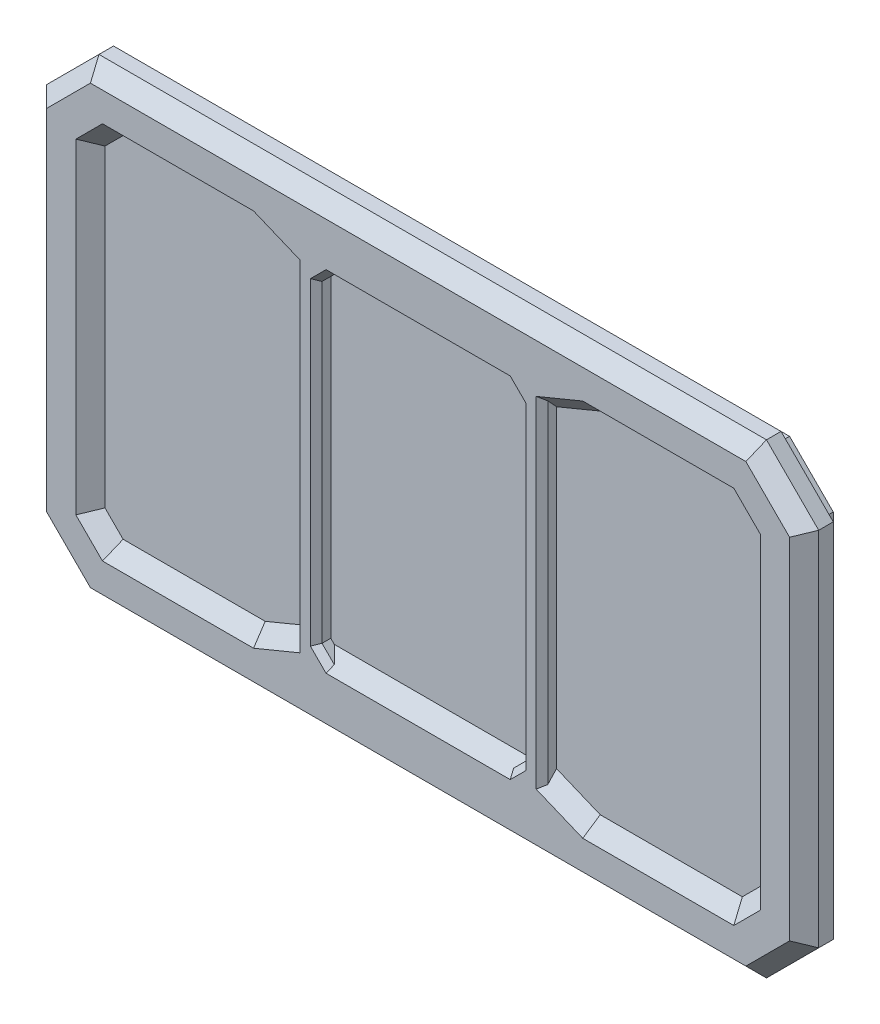
SolidWorks part; units mm, degrees
ref_plane "Plan de face" through (0, 0, 0) normal (0, 0, 1) x (1, 0, 0)
ref_plane "Plan de dessus" through (0, 0, 0) normal (0, 1, 0) x (1, 0, 0)
ref_plane "Plan de droite" through (0, 0, 0) normal (1, 0, 0) x (0, 0, -1)
sketch "Esquisse1" plane through (0, 0, 0) normal (0, 0, 1) x (1, 0, 0)
  line L0 (0, 270) -> (30, 300)
  line L1 (30, 0) -> (480, 0)
  line L2 (0, 30) -> (0, 270)
  line L3 (30, 300) -> (480, 300)
  line L4 (510, 30) -> (510, 270)
  line L5 (30, 0) -> (0, 30)
  line L6 (480, 0) -> (510, 30)
  line L7 (510, 270) -> (480, 300)
  line L8 (10, 265.8579) -> (34.1421, 290)
  line L9 (34.1421, 290) -> (475.8579, 290)
  line L10 (500, 265.8579) -> (475.8579, 290)
  line L11 (500, 34.1421) -> (500, 265.8579)
  line L12 (475.8579, 10) -> (500, 34.1421)
  line L13 (34.1421, 10) -> (475.8579, 10)
  line L14 (34.1421, 10) -> (10, 34.1421)
  line L15 (10, 34.1421) -> (10, 265.8579)
  point P0 (0, 0)
  point P1 (510, 300)
  point P2 (0, 300)
  point P3 (510, 0)
  dimension "D1" = 510
  dimension "D2" = 300
  dimension "D3" = 10
extrude "Boss.-Extru.1" add sketch "Esquisse1" along normal blind 10
sketch "Esquisse2" plane through (0, 0, 10) normal (0, 0, 1) x (1, 0, 0)
  line L17 (484.1421, 310) -> (25.8579, 310)
  line L18 (25.8579, 310) -> (-10, 274.1421)
  line L19 (-10, 274.1421) -> (-10, 25.8579)
  line L20 (-10, 25.8579) -> (25.8579, -10)
  line L21 (25.8579, -10) -> (484.1421, -10)
  line L22 (484.1421, -10) -> (520, 25.8579)
  line L23 (520, 25.8579) -> (520, 274.1421)
  line L24 (520, 274.1421) -> (484.1421, 310)
  line L25 (484.1421, 310) -> (25.8579, 310)
  line L26 (25.8579, 310) -> (-10, 274.1421)
  line L27 (-10, 274.1421) -> (-10, 25.8579)
  line L28 (-10, 25.8579) -> (25.8579, -10)
  line L29 (25.8579, -10) -> (484.1421, -10)
  line L30 (484.1421, -10) -> (520, 25.8579)
  line L31 (520, 25.8579) -> (520, 274.1421)
  line L32 (520, 274.1421) -> (484.1421, 310)
  dimension "D1" = 10
extrude "Boss.-Extru.2" add sketch "Esquisse2" along normal blind 20
sketch "Esquisse3" plane through (0, 0, 30) normal (0, 0, 1) x (1, 0, 0)
  line L8 (255, 270) -> (255, 30) construction
  line L9 (170, 270) -> (170, 30) construction
  line L10 (30, 257.5736) -> (480, 257.5736) construction
  line L11 (480, 42.4264) -> (30, 42.4264) construction
  line L12 (42.4264, 270) -> (140, 270)
  line L13 (140, 270) -> (170, 257.5736)
  line L14 (170, 257.5736) -> (170, 42.4264)
  line L15 (170, 42.4264) -> (140, 30)
  line L16 (480, 257.5736) -> (467.5736, 270)
  line L17 (467.5736, 270) -> (42.4264, 270)
  line L18 (42.4264, 270) -> (30, 257.5736)
  line L19 (30, 257.5736) -> (30, 42.4264)
  line L20 (30, 42.4264) -> (42.4264, 30)
  line L21 (42.4264, 30) -> (467.5736, 30)
  line L22 (467.5736, 30) -> (480, 42.4264)
  line L23 (480, 42.4264) -> (480, 257.5736)
  line L24 (480, 257.5736) -> (467.5736, 270)
  line L25 (467.5736, 270) -> (42.4264, 270) construction
  line L26 (42.4264, 270) -> (30, 257.5736)
  line L27 (30, 257.5736) -> (30, 42.4264)
  line L28 (30, 42.4264) -> (42.4264, 30)
  line L29 (42.4264, 30) -> (467.5736, 30) construction
  line L30 (467.5736, 30) -> (480, 42.4264)
  line L31 (480, 42.4264) -> (480, 257.5736)
  line L32 (140, 270) -> (140, 30) construction
  line L33 (42.4264, 30) -> (42.4264, 42.4264) construction
  line L34 (170, 150) -> (140, 150) construction
  line L35 (185, 270) -> (185, 30) construction
  line L36 (197.4264, 270) -> (197.4264, 30) construction
  line L37 (197.4264, 150) -> (185, 150) construction
  line L38 (197.4264, 270) -> (185, 257.5736)
  line L39 (185, 257.5736) -> (185, 42.4264)
  line L40 (185, 42.4264) -> (197.4264, 30)
  line L41 (255, 270) -> (197.4264, 270)
  line L42 (312.5736, 30) -> (197.4264, 30)
  line L43 (140, 30) -> (42.4264, 30)
  line L44 (467.5736, 270) -> (370, 270)
  line L45 (370, 270) -> (340, 257.5736)
  line L46 (255, 270) -> (312.5736, 270)
  line L47 (312.5736, 270) -> (325, 257.5736)
  line L48 (325, 257.5736) -> (325, 42.4264)
  line L49 (340, 257.5736) -> (340, 42.4264)
  line L50 (340, 42.4264) -> (370, 30)
  line L51 (325, 42.4264) -> (312.5736, 30)
  line L52 (370, 30) -> (467.5736, 30)
  dimension "D2" = 30
  dimension "D3" = 15
  dimension "D4" = 70
  dimension "D1" = 40
extrude "Enlèv. mat.-Extru.1" cut sketch "Esquisse3" against normal blind 10
chamfer "Chanfrein1" distance 10 angle 45 22 edges at (520, 150, 30) (502.0711, 7.9289, 30) (255, -10, 30) (7.9289, 7.9289, 30) (-10, 150, 30) (7.9289, 292.0711, 30) (255, 310, 30) (502.0711, 292.0711, 30) (473.7868, 263.7868, 30) (418.7868, 270, 30) (355, 263.7868, 30) (355, 36.2132, 30) (418.7868, 30, 30) (473.7868, 36.2132, 30) (480, 150, 30) (155, 36.2132, 30) (155, 263.7868, 30) (91.2132, 270, 30) (36.2132, 263.7868, 30) (30, 150, 30) (36.2132, 36.2132, 30) (91.2132, 30, 30)
chamfer "Chanfrein2" distance 10 angle 45 2 edges at (255, 30, 20) (255, 270, 20)
chamfer "Chanfrein3" distance 4 angle 45 8 edges at (325, 150, 30) (340, 150, 30) (185, 150, 30) (170, 150, 30) (318.7868, 36.2132, 30) (318.7868, 263.7868, 30) (191.2132, 36.2132, 30) (191.2132, 263.7868, 30)
